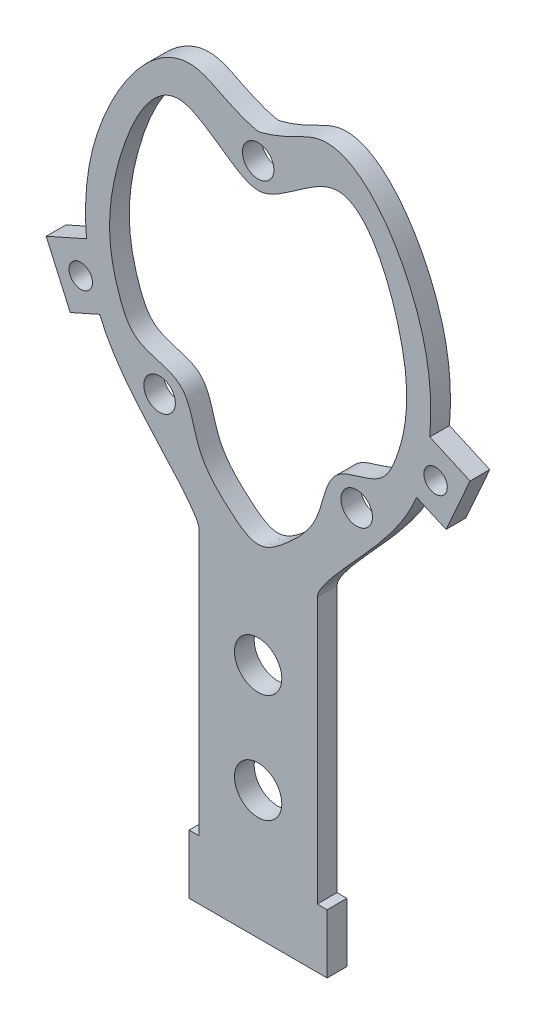
SolidWorks part; units mm, degrees
ref_plane "Front Plane" through (0, 0, 0) normal (0, 0, 1) x (1, 0, 0)
ref_plane "Top Plane" through (0, 0, 0) normal (0, 1, 0) x (1, 0, 0)
ref_plane "Right Plane" through (0, 0, 0) normal (1, 0, 0) x (0, 0, -1)
sketch "Sketch2" plane through (0, 0, 0) normal (0, 0, 1) x (1, 0, 0)
  line L0 (0, -0.0188) -> (0, -6.781) construction
  line L1 (-1.25, 4.75) -> (1.25, 4.75) construction
  line L2 (-4, 6.25) -> (4, 6.25) construction
  line L3 (-7.2, 1.5) -> (7.2, 1.5) construction
  line L4 (-6.25, -5.25) -> (6.25, -5.25) construction
  line L5 (-4, -6.25) -> (4, -6.25) construction
  line L6 (-3, -8.55) -> (3, -8.55) construction
  line L7 (-1.4, -10.55) -> (1.4, -10.55) construction
  line L8 (-5, -7.2) -> (-6.1491, -8.1642) construction
  line L9 (-7, -4) -> (7, -4) construction
  line L10 (0, 1.0146) -> (0, -5.7476) construction
  line L11 (-1, 7.15) -> (1, 7.15) construction
  line L12 (-3.1, 8.05) -> (3.1, 8.05) construction
  line L13 (-8.4144, 1.7962) -> (8.4144, 1.7962) construction
  line L14 (-6.1491, -8.1642) -> (6.1491, -8.1642) construction
  line L16 (-0.5007, -40.6671) -> (-6.3266, 25.9227) construction
  line L17 (-3, -12.1) -> (3, -12.1) construction
  line L18 (-8.6856, -2.4538) -> (8.6856, -2.4538) construction
  line L19 (6.2221, 24.7292) -> (0.3963, -41.8606) construction
  line L20 (-28.4032, 6.85) -> (28.4032, 6.85) construction
  line L21 (-7.2, 1.5) -> (-8.4144, 1.7962) construction
  line L22 (-8.6856, -2.4538) -> (-7.4495, -2.2683) construction
  line L23 (-3, -25.6) -> (-3.5, -25.6)
  line L24 (-3, -12.1) -> (3, -12.1) construction
  line L25 (-3, -12.1) -> (-3, -25.6)
  line L26 (-3, -25.6) -> (3, -25.6) construction
  line L27 (3, -12.1) -> (3, -25.6)
  line L28 (-3, -12.1) -> (3, -25.6) construction
  line L29 (-3, -25.6) -> (3, -12.1) construction
  line L30 (-3.5, -25.6) -> (3.5, -25.6) construction
  line L31 (-3.5, -25.6) -> (-3.5, -28.6)
  line L32 (-3.5, -28.6) -> (3.5, -28.6)
  line L33 (3.5, -25.6) -> (3.5, -28.6)
  line L34 (-3.5, -25.6) -> (3.5, -28.6) construction
  line L35 (-3.5, -28.6) -> (3.5, -25.6) construction
  line L36 (3.5, -25.6) -> (3, -25.6)
  circle A2 centre (0, -16.6) radius 1.2
  circle A3 centre (0, 5.55) radius 0.8
  circle A4 centre (-5, -7.2) radius 0.8
  circle A5 centre (5, -7.2) radius 0.8
  circle A6 centre (0, -22.1) radius 1.2
  spline S0 degree 3 poles (1.8069, 5.0163) (0, 4.0197) (-1.8069, 5.0163) (-4.9012, 7.7541) (-7.771, 1.1281) (-7.6313, -2.6614) (-6.2568, -5.758) (-3.5015, -5.7609) (-3.2301, -8.7844) (-1.7453, -10.314) (0, -11.6774) (1.7453, -10.314) (3.2301, -8.7844) (3.5015, -5.7609) (6.2568, -5.758) (7.6313, -2.6614) (7.771, 1.1281) (4.9012, 7.7541) (1.8069, 5.0163) (0, 4.0197) (-1.8069, 5.0163) knots -0.194127 -0.085189 -0.025607 0 0.025607 0.085189 0.194127 0.29881 0.326537 0.37337 0.421074 0.469791 0.5 0.530209 0.578926 0.62663 0.673463 0.70119 0.805873 0.914811 0.974393 1 1.025607 1.085189 1.194127 only from (0, 4.25) to (0, 4.25)
  spline S1 degree 3 poles (3, -12.1) (3.0581, -11.4359) (7.3722, -7.2617) (8.8163, -3.8196) (8.7952, 3.0882) (4.7299, 9.5027) (1.5431, 7.2852) (0.1384, 6.8487) (-0.1384, 6.8487) (-1.5431, 7.2852) (-4.7299, 9.5027) (-8.7952, 3.0882) (-8.8163, -3.8196) (-7.3722, -7.2617) (-3.0581, -11.4359) (-3, -12.1) knots 0.110532 0.110532 0.110532 0.110532 0.195871 0.310872 0.37508 0.502014 0.537662 0.553506 0.557026 0.57287 0.608518 0.735452 0.79966 0.914661 1 1 1 1
  point P5 (0, 0)
  point P9 (0, -6.25)
  point P40 (0, -2.2618)
  point P45 (0, -27.1)
  point P51 (0, 4.75)
  point P58 (0, 6.25)
  point P60 (0, 1.5)
  point P62 (0, -4)
  point P64 (0, -5.25)
  point P68 (0, -8.55)
  point P86 (0, -12.1)
  point P89 (0, 7.15)
  point P90 (0, 8.05)
  point P91 (0, 1.7962)
  point P92 (0, -2.4538)
  point P93 (0, -8.1642)
  point P100 (0, -10.55)
  point P101 (0, -25.6)
  point P102 (0, -18.85)
  dimension "D32" = 1
  dimension "D36" = 2
  dimension "D37" = 2
  dimension "D40" = 1.6
  dimension "D6" = 0.5
  dimension "D46" = 2.4
  dimension "D1" = 6
  dimension "D2" = 13.5
  dimension "D3" = 1.5
  dimension "D5" = 7.2
  dimension "D7" = 2.6
  dimension "D8" = 4.25
  dimension "D9" = 1.25
  dimension "D10" = 2
  dimension "D11" = 4
  dimension "D12" = 0.3
  dimension "D13" = 0.9
  dimension "D14" = 3.1
  dimension "D15" = 4
  dimension "D16" = 7
  dimension "D17" = 1.25
  dimension "D18" = 5.25
  dimension "D19" = 6.25
  dimension "D20" = 6.25
  dimension "D21" = 4
  dimension "D22" = 8.55
  dimension "D23" = 3
  dimension "D24" = 1.5
  dimension "D25" = 40
  dimension "D27" = 10.55
  dimension "D28" = 1.4
  dimension "D29" = 11.3
  dimension "D31" = 0.8
  dimension "D33" = 90
  dimension "D34" = 1
  dimension "D35" = 1.25
  dimension "D38" = 175
  dimension "D39" = 175
  dimension "D41" = 1.3
  dimension "D42" = 12.75
  dimension "D43" = 5
  dimension "D44" = 3
  dimension "D45" = 7
  dimension "D47" = 3.5
  dimension "D48" = 5.5
extrude "Boss-Extrude2" add sketch "Sketch2" along normal blind 1 separate body
sketch "Sketch3" plane through (0, 0, 0) normal (0, 0, 1) x (1, 0, 0)
  line L0 (-7.4013, -3.2882) -> (-10.1419, -4.5084) construction
  line L5 (-8.0114, -1.9179) -> (-6.7912, -4.6585)
  line L6 (-8.0114, -1.9179) -> (-10.752, -3.1381)
  line L8 (-10.752, -3.1381) -> (-9.5318, -5.8787)
  line L9 (-6.7912, -4.6585) -> (-9.5318, -5.8787)
  line L10 (0, 0) -> (0, -5.2835) construction
  line L11 (-8.0114, -1.9179) -> (-10.752, -3.1381)
  line L12 (-6.7912, -4.6585) -> (-9.5318, -5.8787)
  line L13 (7.4013, -3.2882) -> (10.1419, -4.5084) construction
  line L14 (6.7912, -4.6585) -> (9.5318, -5.8787)
  line L15 (8.0114, -1.9179) -> (10.752, -3.1381)
  line L16 (6.7912, -4.6585) -> (9.5318, -5.8787)
  line L17 (10.752, -3.1381) -> (9.5318, -5.8787)
  line L18 (8.0114, -1.9179) -> (10.752, -3.1381)
  line L19 (8.0114, -1.9179) -> (6.7912, -4.6585)
  point P5 (-9, -4)
  point P25 (9, -4)
  dimension "D1" = 3
  dimension "D2" = 24
  dimension "D3" = 1.25
  dimension "D4" = 9
  dimension "D5" = 4
extrude "Boss-Extrude3" add sketch "Sketch3" along normal blind 1 contours L9 L5 L6 L8 | L15 L19 L14 L17 region at (-8.7716, -3.8983, 0) region at (8.7716, -3.8983, 0)
sketch "Sketch4" plane through (0, 0, 0) normal (0, 0, 1) x (1, 0, 0)
  line L0 (-10.1419, -4.5084) -> (-9, -4) construction
  line L3 (-10.752, -3.1381) -> (-9.5318, -5.8787) construction
  line L6 (-8.7065, -2.2274) -> (-10.752, -3.1381) construction
  line L7 (0, 0) -> (0, -3.1391) construction
  circle A0 centre (-9, -4) radius 0.595
  circle A2 centre (9, -4) radius 0.595
  dimension "D1" = 1.19
  dimension "D2" = 1.25
extrude "Cut-Extrude10" cut sketch "Sketch4" along normal blind 10
